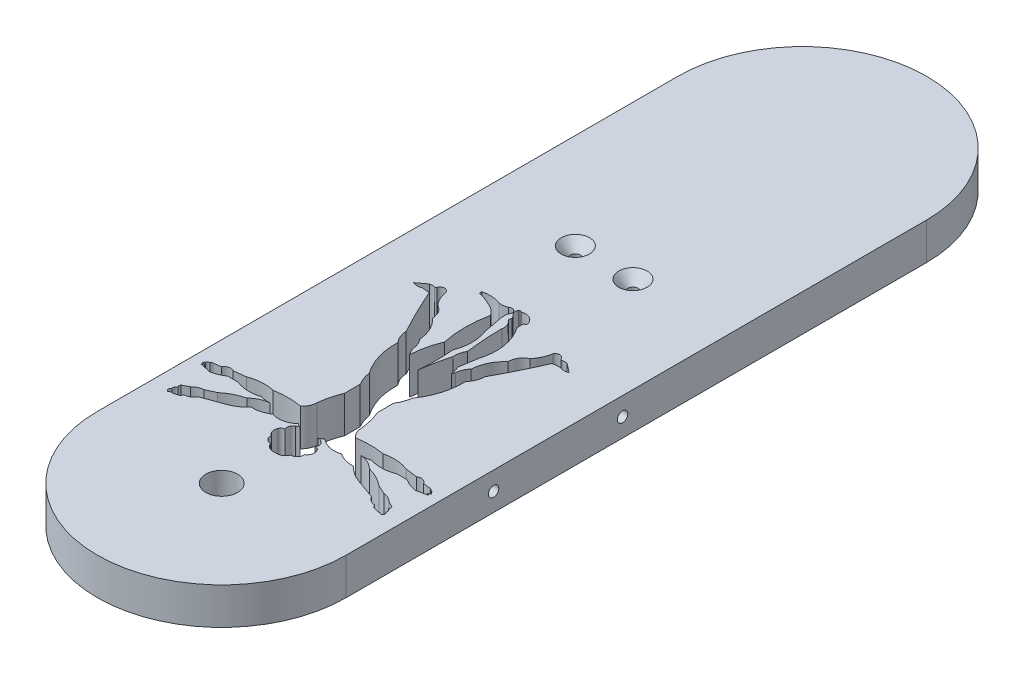
SolidWorks part; units mm, degrees
ref_plane "Front Plane" through (0, 0, 0) normal (0, 0, 1) x (1, 0, 0)
ref_plane "Top Plane" through (0, 0, 0) normal (0, 1, 0) x (1, 0, 0)
ref_plane "Right Plane" through (0, 0, 0) normal (1, 0, 0) x (0, 0, -1)
sketch "Sketch1" plane through (0, 0, 0) normal (0, 1, 0) x (1, 0, 0)
  line L0 (34.29, 228.6) -> (34.29, 0) construction
  line L1 (0, 0) -> (68.58, 0)
  line L2 (0, 0) -> (0, 194.31)
  line L4 (68.58, 0) -> (68.58, 194.31)
  arc A0 (0, 194.31) -> (68.58, 194.31) centre (34.29, 194.31) cw
  circle A1 centre (42.2275, 139.7) radius 1.3589
  circle A2 centre (26.3525, 139.7) radius 1.3589
  circle A3 centre (34.29, 34.29) radius 4.3815
  dimension "D2" = 2.7178
  dimension "D6" = 8.763
  dimension "D1" = 139.7
  dimension "D3" = 7.9375
  dimension "D4" = 68.58
  dimension "D5" = 228.6
  dimension "D7" = 34.29
extrude "Boss-Extrude1" add sketch "Sketch1" along normal blind 10.16 contours L0 A0 L2 L1 A3 A2 | A0 L0 A3 L1 L4 A1 region at (51.1861, 0, -111.0362) region at (17.3939, 0, -111.0362)
sketch "Sketch2" plane through (0, 10.16, 0) normal (0, 1, 0) x (1, 0, 0)
  line L0 (37.6657, 49.1626) -> (12.67, 49.1626) construction
sketch "Sketch3" plane through (0, 10.16, 0) normal (0, 1, 0) x (1, 0, 0)
  line L0 (34.29, 44.1322) -> (34.29, 49.022) construction
  line L1 (16.0215, 53.7464) -> (10.4335, 51.7461)
  line L2 (8.1475, 50.2221) -> (7.4635, 49.4709)
  line L3 (7.4635, 49.4709) -> (5.8739, 49.0246)
  line L4 (5.5691, 49.1516) -> (4.8952, 48.796)
  line L5 (5.2762, 52.1488) -> (6.9835, 53.0497)
  line L6 (9.5235, 54.2181) -> (12.0615, 55.3865)
  line L7 (12.3155, 60.7046) -> (9.5215, 60.7046)
  line L8 (7.5911, 59.6886) -> (6.0671, 59.2608)
  line L9 (6.0671, 59.2608) -> (3.0191, 59.8958)
  line L10 (3.5164, 60.3002) -> (2.8814, 60.4526)
  line L11 (4.4181, 61.8242) -> (6.4501, 62.0782)
  line L12 (8.9901, 62.7132) -> (12.2921, 63.1259)
  line L13 (29.7165, 72.7271) -> (29.7165, 77.0451)
  line L14 (17.3467, 108.4395) -> (15.3147, 108.5919)
  line L15 (12.7747, 108.5919) -> (15.3147, 110.4969)
  line L16 (24.3978, 115.2304) -> (24.3978, 115.8654)
  line L17 (34.9642, 113.5979) -> (34.4562, 114.4778)
  line L18 (37.8399, 113.9698) -> (37.8399, 112.1252)
  line L19 (39.8719, 99.4252) -> (39.1099, 94.6597)
  line L20 (34.3038, 106.8669) -> (33.2878, 112.3279)
  line L21 (55.8053, 108.5919) -> (53.2653, 110.4969)
  line L22 (51.2333, 108.4395) -> (53.2653, 108.5919)
  line L23 (38.8635, 72.7271) -> (38.8635, 77.0451)
  line L24 (59.5899, 62.7132) -> (56.2879, 63.1259)
  line L25 (64.1619, 61.8242) -> (62.1299, 62.0782)
  line L26 (65.0636, 60.3002) -> (65.6986, 60.4526)
  line L27 (62.5129, 59.2608) -> (65.5609, 59.8958)
  line L28 (60.9889, 59.6886) -> (62.5129, 59.2608)
  line L29 (56.2645, 60.7046) -> (59.0585, 60.7046)
  line L30 (59.0565, 54.2181) -> (56.5185, 55.3865)
  line L31 (63.3038, 52.1488) -> (61.5965, 53.0497)
  line L32 (63.0109, 49.1516) -> (63.6848, 48.796)
  line L33 (61.1165, 49.4709) -> (62.7061, 49.0246)
  line L34 (60.4325, 50.2221) -> (61.1165, 49.4709)
  line L35 (52.5585, 53.7464) -> (58.1465, 51.7461)
  line L36 (0, 0) -> (68.58, 0) construction
  line L37 (34.29, 0) -> (34.29, 228.6) construction
  arc A0 (30.6265, 59.1058) -> (24.7845, 57.8358) centre (26.6393, 63.3756) cw
  arc A1 (24.7845, 57.8358) -> (20.2125, 56.5404) centre (20.5978, 63.8963) cw
  arc A2 (20.2125, 56.5404) -> (16.0215, 53.7464) centre (12.5118, 63.5512) cw
  arc A3 (10.4335, 51.7461) -> (8.1475, 50.2221) centre (7.9734, 52.9598) cw
  arc A4 (5.8739, 49.0246) -> (5.5691, 49.1516) centre (5.8536, 49.4051) cw
  arc A5 (4.8952, 48.796) -> (4.7682, 50.066) centre (5.1441, 49.4623) cw
  arc A6 (4.7682, 50.066) -> (5.2762, 51.2344) centre (5.5909, 50.403) cw
  arc A7 (5.2762, 51.2344) -> (5.2762, 52.1488) centre (5.7528, 51.6916) cw
  arc A8 (6.9835, 53.0497) -> (9.5235, 54.2181) centre (9.7347, 50.4139) cw
  arc A9 (12.0615, 55.3865) -> (17.3955, 58.1043) centre (20.4503, 45.5156) cw
  arc A10 (29.4778, 90.8649) -> (31.2558, 98.7389) centre (52.3151, 89.8458) cw
  arc A11 (17.3955, 58.1043) -> (21.7135, 60.1363) centre (22.4072, 53.0582) cw
  arc A12 (21.7135, 60.1363) -> (19.1735, 60.4506) centre (21.1436, 65.9504) cw
  arc A13 (19.1735, 60.4506) -> (12.3155, 60.7046) centre (16.0984, 70.1341) cw
  arc A14 (9.5215, 60.7046) -> (7.5911, 59.6886) centre (4.4828, 67.9363) cw
  arc A15 (3.0191, 59.8958) -> (3.5164, 60.3002) centre (3.5164, 59.7922) cw
  arc A16 (2.8814, 60.4526) -> (3.1989, 60.9606) centre (3.3331, 60.5235) cw
  arc A17 (3.1989, 60.9606) -> (3.9101, 61.4686) centre (3.8223, 60.8397) cw
  arc A18 (3.9101, 61.4686) -> (4.4181, 61.8242) centre (4.3568, 61.3711) cw
  arc A19 (6.4501, 62.0782) -> (8.9901, 62.7132) centre (8.0119, 61.2284) cw
  arc A20 (12.2921, 63.1259) -> (19.1501, 63.5831) centre (16.4462, 52.4775) cw
  arc A21 (19.1501, 63.5831) -> (26.7701, 63.5831) centre (22.9601, 41.5582) cw
  arc A22 (26.7701, 63.5831) -> (28.1925, 66.6311) centre (23.8774, 66.7889) ccw
  arc A23 (28.1925, 66.6311) -> (29.7165, 72.7271) centre (49.926, 64.4363) cw
  arc A24 (29.7165, 77.0451) -> (28.2687, 81.0075) centre (39.544, 82.8816) cw
  arc A25 (28.2687, 81.0075) -> (24.9667, 92.1835) centre (43.2422, 91.5073) cw
  arc A26 (24.9667, 92.1835) -> (23.4427, 95.9935) centre (29.2833, 96.12) cw
  arc A27 (23.4427, 95.9935) -> (17.3467, 108.4395) centre (162.598, 171.8671) cw
  arc A28 (15.3147, 108.5919) -> (12.7747, 108.5919) centre (14.0447, 111.9134) cw
  arc A29 (15.3147, 110.4969) -> (16.7103, 110.4969) centre (16.0125, 108.0546) cw
  arc A30 (16.7103, 110.4969) -> (17.1861, 110.6747) centre (16.7942, 110.9979) ccw
  arc A31 (17.1861, 110.6747) -> (19.5718, 110.8293) centre (18.4067, 110.3239) cw
  arc A32 (19.5718, 110.8293) -> (21.6038, 106.5113) centre (28.3365, 112.3167) ccw
  arc A33 (21.6038, 106.5113) -> (23.8898, 102.8029) centre (19.8262, 102.8567) cw
  arc A34 (23.8898, 102.8029) -> (27.1918, 95.9449) centre (17.0531, 95.2872) cw
  arc A35 (27.1918, 95.9449) -> (28.4618, 92.8969) centre (23.3921, 92.5731) cw
  arc A36 (28.4618, 92.8969) -> (29.4778, 90.8649) centre (37.0851, 95.9385) ccw
  arc A37 (40.1182, 92.8969) -> (39.8033, 92.1197) centre (31.4949, 95.9385) cw
  arc A38 (41.3882, 95.9449) -> (40.1182, 92.8969) centre (45.1879, 92.5731) ccw
  arc A39 (31.2558, 98.7389) -> (31.2558, 111.4389) centre (61.067, 105.0889) cw
  arc A40 (31.2558, 111.4389) -> (28.9698, 113.4709) centre (25.8446, 107.6532) ccw
  arc A43 (24.3978, 115.8654) -> (29.4778, 115.5606) centre (26.4595, 107.7409) cw
  arc A44 (29.4778, 115.5606) -> (31.7638, 115.8146) centre (30.1904, 119.5617) ccw
  arc A45 (31.7638, 115.8146) -> (33.2878, 114.1795) centre (32.5258, 114.9971) cw
  arc A46 (33.2878, 114.1795) -> (33.2878, 112.3279) centre (39.056, 113.2537) ccw
  arc A47 (44.6902, 102.8029) -> (41.3882, 95.9449) centre (51.5269, 95.2872) ccw
  arc A48 (34.3038, 106.8669) -> (34.3038, 97.9769) centre (22.951, 102.4219) cw
  arc A49 (34.3038, 97.9769) -> (34.3038, 88.3249) centre (-18.0522, 93.1509) cw
  arc A50 (34.3038, 88.3249) -> (35.904, 96.4529) centre (90.5303, 81.4768) cw
  arc A51 (35.904, 96.4529) -> (36.666, 99.6279) centre (41.2228, 96.8553) cw
  arc A52 (36.666, 99.6279) -> (35.9802, 109.7879) centre (122.3372, 110.5138) cw
  arc A53 (35.9802, 109.7879) -> (34.9642, 112.5819) centre (33.2489, 110.3764) ccw
  arc A54 (34.9642, 112.5819) -> (34.9642, 113.5979) centre (35.5322, 113.0899) cw
  arc A55 (34.4562, 114.4778) -> (33.9482, 116.5098) centre (35.172, 115.7362) cw
  arc A56 (33.9482, 116.5098) -> (34.6594, 116.4336) centre (34.2654, 116.1129) cw
  arc A57 (34.6594, 116.4336) -> (38.3678, 114.6556) centre (35.6958, 113.8389) cw
  arc A58 (38.3678, 114.6556) -> (37.8399, 113.9698) centre (37.893, 114.475) cw
  arc A59 (37.8399, 112.1252) -> (39.8719, 99.4252) centre (26.0474, 103.7258) cw
  arc A60 (39.1099, 94.6597) -> (39.8033, 92.1197) centre (25.0555, 89.4582) cw
  arc A61 (30.6265, 59.1058) -> (31.817, 58.3438) centre (33.9337, 62.9618) ccw
  arc A62 (34.29, 49.022) -> (31.496, 50.546) centre (33.7777, 51.406) cw
  arc A63 (31.496, 50.546) -> (29.718, 52.578) centre (31.4778, 52.3239) cw
  arc A64 (29.718, 52.578) -> (28.956, 55.118) centre (30.6471, 54.241) cw
  arc A65 (28.956, 55.118) -> (30.1152, 55.88) centre (29.9434, 54.8786) cw
  arc A66 (30.1152, 55.88) -> (30.801, 58.0898) centre (31.4278, 56.684) cw
  arc A67 (30.801, 58.0898) -> (31.817, 58.3438) centre (31.4677, 57.5818) cw
  arc A68 (46.9762, 106.5113) -> (44.6902, 102.8029) centre (48.7538, 102.8567) ccw
  arc A69 (49.0082, 110.8293) -> (46.9762, 106.5113) centre (40.2435, 112.3167) cw
  arc A70 (51.3939, 110.6747) -> (49.0082, 110.8293) centre (50.1733, 110.3239) ccw
  arc A71 (51.8697, 110.4969) -> (51.3939, 110.6747) centre (51.7858, 110.9979) cw
  arc A72 (53.2653, 110.4969) -> (51.8697, 110.4969) centre (52.5675, 108.0546) ccw
  arc A73 (53.2653, 108.5919) -> (55.8053, 108.5919) centre (54.5353, 111.9134) ccw
  arc A74 (45.1373, 95.9935) -> (51.2333, 108.4395) centre (-94.018, 171.8671) ccw
  arc A75 (43.6133, 92.1835) -> (45.1373, 95.9935) centre (39.2967, 96.12) ccw
  arc A76 (40.3113, 81.0075) -> (43.6133, 92.1835) centre (25.3378, 91.5073) ccw
  arc A77 (38.8635, 77.0451) -> (40.3113, 81.0075) centre (29.036, 82.8816) ccw
  arc A78 (37.779, 58.0898) -> (36.763, 58.3438) centre (37.1123, 57.5818) ccw
  arc A79 (38.4648, 55.88) -> (37.779, 58.0898) centre (37.1522, 56.684) ccw
  arc A80 (39.624, 55.118) -> (38.4648, 55.88) centre (38.6366, 54.8786) ccw
  arc A81 (38.862, 52.578) -> (39.624, 55.118) centre (37.9329, 54.241) ccw
  arc A82 (37.084, 50.546) -> (38.862, 52.578) centre (37.1022, 52.3239) ccw
  arc A83 (34.29, 49.022) -> (37.084, 50.546) centre (34.8023, 51.406) ccw
  arc A84 (37.9535, 59.1058) -> (36.763, 58.3438) centre (34.6463, 62.9618) cw
  arc A85 (40.3875, 66.6311) -> (38.8635, 72.7271) centre (18.654, 64.4363) ccw
  arc A86 (41.8099, 63.5831) -> (40.3875, 66.6311) centre (44.7026, 66.7889) cw
  arc A87 (49.4299, 63.5831) -> (41.8099, 63.5831) centre (45.6199, 41.5582) ccw
  arc A88 (56.2879, 63.1259) -> (49.4299, 63.5831) centre (52.1338, 52.4775) ccw
  arc A89 (62.1299, 62.0782) -> (59.5899, 62.7132) centre (60.5681, 61.2284) ccw
  arc A90 (64.6699, 61.4686) -> (64.1619, 61.8242) centre (64.2232, 61.3711) ccw
  arc A91 (65.3811, 60.9606) -> (64.6699, 61.4686) centre (64.7577, 60.8397) ccw
  arc A92 (65.6986, 60.4526) -> (65.3811, 60.9606) centre (65.2469, 60.5235) ccw
  arc A93 (65.5609, 59.8958) -> (65.0636, 60.3002) centre (65.0636, 59.7922) ccw
  arc A94 (59.0585, 60.7046) -> (60.9889, 59.6886) centre (64.0972, 67.9363) ccw
  arc A95 (49.4065, 60.4506) -> (56.2645, 60.7046) centre (52.4816, 70.1341) ccw
  arc A96 (46.8665, 60.1363) -> (49.4065, 60.4506) centre (47.4364, 65.9504) ccw
  arc A97 (51.1845, 58.1043) -> (46.8665, 60.1363) centre (46.1728, 53.0582) ccw
  arc A98 (56.5185, 55.3865) -> (51.1845, 58.1043) centre (48.1297, 45.5156) ccw
  arc A99 (61.5965, 53.0497) -> (59.0565, 54.2181) centre (58.8453, 50.4139) ccw
  arc A100 (63.3038, 51.2344) -> (63.3038, 52.1488) centre (62.8272, 51.6916) ccw
  arc A101 (63.8118, 50.066) -> (63.3038, 51.2344) centre (62.9891, 50.403) ccw
  arc A102 (63.6848, 48.796) -> (63.8118, 50.066) centre (63.4359, 49.4623) ccw
  arc A103 (62.7061, 49.0246) -> (63.0109, 49.1516) centre (62.7264, 49.4051) ccw
  arc A104 (58.1465, 51.7461) -> (60.4325, 50.2221) centre (60.6066, 52.9598) ccw
  arc A105 (48.3675, 56.5404) -> (52.5585, 53.7464) centre (56.0682, 63.5512) ccw
  arc A106 (43.7955, 57.8358) -> (48.3675, 56.5404) centre (47.9822, 63.8963) ccw
  arc A107 (37.9535, 59.1058) -> (43.7955, 57.8358) centre (41.9407, 63.3756) ccw
  arc A108 (28.9698, 113.4709) -> (24.3978, 115.2304) centre (19.7144, 96.2415) ccw
  arc A110 (68.58, 194.31) -> (0, 194.31) centre (34.29, 194.31) ccw construction
  circle A111 centre (34.29, 34.29) radius 4.3815 construction
  point P178 (18.3246, 111.5913)
  dimension "D1" = 2.4384
  dimension "D2" = 1.778
  dimension "D3" = 1.905
  dimension "D4" = 1.016
  dimension "D5" = 1.5392
  dimension "D6" = 0.8382
  dimension "D7" = 5.08
  dimension "D8" = 5.842
  dimension "D9" = 7.366
  dimension "D10" = 10.414
  dimension "D31" = 2.7432
  dimension "D37" = 0.381
  dimension "D43" = 0.7112
  dimension "D44" = 0.889
  dimension "D45" = 0.6604
  dimension "D47" = 3.81
  dimension "D49" = 12.954
  dimension "D50" = 7.112
  dimension "D51" = 4.318
  dimension "D52" = 5.842
  dimension "D53" = 10.16
  dimension "D68" = 8.8139
  dimension "D74" = 0.508
  dimension "D78" = 0.4572
  dimension "D82" = 0.635
  dimension "D85" = 0.4572
  dimension "D90" = 1.778
  dimension "D94" = 11.43
  dimension "D98" = 22.352
  dimension "D99" = 4.318
  dimension "D102" = 21.844
  dimension "D106" = 11.43
  dimension "D111" = 18.288
  dimension "D112" = 5.842
  dimension "D115" = 158.496
  dimension "D119" = 3.556
  dimension "D123" = 2.54
  dimension "D126" = 0.508
  dimension "D127" = 1.27
  dimension "D132" = 8.89
  dimension "D135" = 4.064
  dimension "D138" = 10.16
  dimension "D141" = 5.08
  dimension "D143" = 9.144
  dimension "D147" = 22.86
  dimension "D148" = 30.48
  dimension "D149" = 7.874
  dimension "D151" = 6.604
  dimension "D154" = 52.578
  dimension "D156" = 12.192
  dimension "D157" = 56.642
  dimension "D166" = 19.558
  dimension "D168" = 8.382
  dimension "D172" = 4.064
  dimension "D173" = 1.1176
  dimension "D177" = 5.842
  dimension "D178" = 14.986
  dimension "D184" = 5.334
  dimension "D187" = 86.36
  dimension "D188" = 14.478
  dimension "D193" = 2.794
  dimension "D196" = 0.762
  dimension "D200" = 1.4478
  dimension "D203" = 0.508
  dimension "D204" = 2.794
  dimension "D205" = 0.508
  dimension "D211" = 14.732
  dimension "D12" = 1.524
  dimension "D13" = 2.032
  dimension "D14" = 2.794
  dimension "D15" = 1.778
  dimension "D16" = 2.54
  dimension "D17" = 0.762
  dimension "D18" = 0.762
  dimension "D19" = 1.1592
  dimension "D20" = 2.2098
  dimension "D21" = 0.6858
  dimension "D22" = 0.254
  dimension "D23" = 1.016
  dimension "D24" = 5.842
  dimension "D25" = 1.27
  dimension "D26" = 4.572
  dimension "D27" = 1.2954
  dimension "D28" = 0.762
  dimension "D29" = 4.191
  dimension "D30" = 2.794
  dimension "D32" = 1.016
  dimension "D33" = 1.651
  dimension "D34" = 1.524
  dimension "D35" = 2.286
  dimension "D36" = 5.588
  dimension "D38" = 0.3048
  dimension "D39" = 0.127
  dimension "D40" = 0.762
  dimension "D41" = 0.3556
  dimension "D42" = 148
  dimension "D46" = 1.9304
  dimension "D48" = 2.794
  dimension "D54" = 0.127
  dimension "D55" = 1.27
  dimension "D56" = 0.508
  dimension "D57" = 1.1684
  dimension "D58" = 0.9144
  dimension "D59" = 1.1684
  dimension "D60" = 2.54
  dimension "D61" = 1.1684
  dimension "D62" = 2.7178
  dimension "D63" = 5.334
  dimension "D64" = 2.032
  dimension "D65" = 6.858
  dimension "D66" = 0.254
  dimension "D67" = 2.54
  dimension "D69" = 1.524
  dimension "D70" = 1.9304
  dimension "D71" = 1.016
  dimension "D72" = 2.794
  dimension "D73" = 3.048
  dimension "D75" = 0.635
  dimension "D76" = 0.635
  dimension "D77" = 0.508
  dimension "D79" = 0.4044
  dimension "D80" = 0.1524
  dimension "D81" = 0.3175
  dimension "D83" = 0.7112
  dimension "D84" = 0.508
  dimension "D86" = 0.3556
  dimension "D87" = 0.508
  dimension "D88" = 2.032
  dimension "D89" = 0.254
  dimension "D91" = 0.635
  dimension "D92" = 2.54
  dimension "D93" = 3.302
  dimension "D95" = 6.858
  dimension "D96" = 0.4572
  dimension "D97" = 7.62
  dimension "D100" = 1.4224
  dimension "D101" = 3.048
  dimension "D103" = 6.096
  dimension "D104" = 1.524
  dimension "D105" = 4.318
  dimension "D107" = 3.9624
  dimension "D108" = 1.4478
  dimension "D109" = 3.302
  dimension "D110" = 11.176
  dimension "D113" = 3.81
  dimension "D114" = 1.524
  dimension "D116" = 6.096
  dimension "D117" = 12.446
  dimension "D118" = 2.032
  dimension "D120" = 0.1524
  dimension "D121" = 2.54
  dimension "D122" = 3.175
  dimension "D124" = 1.3956
  dimension "D125" = 2.54
  dimension "D128" = 0.4758
  dimension "D129" = 0.1778
  dimension "D130" = 0.1546
  dimension "D131" = 0.762
  dimension "D133" = 4.318
  dimension "D134" = 2.032
  dimension "D136" = 2.286
  dimension "D137" = 3.7084
  dimension "D139" = 6.858
  dimension "D140" = 3.302
  dimension "D142" = 1.27
  dimension "D144" = 3.048
  dimension "D145" = 2.032
  dimension "D146" = 1.016
  dimension "D150" = 1.778
  dimension "D152" = 12.7
  dimension "D153" = 9.652
  dimension "D155" = 8.89
  dimension "D158" = 1.6002
  dimension "D159" = 8.128
  dimension "D160" = 2.54
  dimension "D161" = 4.826
  dimension "D162" = 1.016
  dimension "D163" = 5.461
  dimension "D164" = 2.286
  dimension "D165" = 2.032
  dimension "D167" = 0.635
  dimension "D169" = 6.858
  dimension "D170" = 5.08
  dimension "D171" = 0.3048
  dimension "D174" = 2.286
  dimension "D175" = 0.254
  dimension "D176" = 2.2352
  dimension "D179" = 0.6934
  dimension "D180" = 2.54
  dimension "D181" = 3.81
  dimension "D182" = 4.826
  dimension "D183" = 0.762
  dimension "D185" = 0.762
  dimension "D186" = 3.175
  dimension "D189" = 2.032
  dimension "D190" = 0.6858
  dimension "D191" = 12.7
  dimension "D192" = 10.16
  dimension "D194" = 1.016
  dimension "D195" = 2.794
  dimension "D197" = 1.016
  dimension "D198" = 1.016
  dimension "D199" = 0.508
  dimension "D201" = 0.508
  dimension "D202" = 2.032
  dimension "D206" = 0.0762
  dimension "D207" = 0.7112
  dimension "D208" = 1.778
  dimension "D209" = 3.7084
  dimension "D210" = 0.6858
extrude "Cut-Extrude1" cut sketch "Sketch3" against normal through all
fillet "Fillet1" 2 edges at (0, 5.08, 0) (68.58, 5.08, 0) type full round first side face at (0, 5.08, -97.155) second side face at (68.58, 5.08, -97.155) middle face at (34.29, 5.08, 0)
hole_wizard "CSK for #3 Flat Head Machine Screw1" positions "Sketch6" profile "Sketch7" countersink size "#3" standard "ANSI Inch" end condition through all
sketch "Sketch6" plane through (0, 10.16, 0) normal (0, 1, 0) x (1, 0, 0)
  point P0 (42.2275, 139.7)
  point P3 (26.3525, 139.7)
sketch "Sketch7" plane through (42.2275, 10.16, -139.7) normal (1, 0, 0) x (0, 0, 1)
  line L0 (0, 0) -> (0, 10.16)
  line L1 (0, 10.16) -> (1.397, 10.16)
  line L2 (1.397, 10.16) -> (1.397, 2.8781)
  line L3 (1.397, 2.8781) -> (3.8989, 0)
  line L5 (3.8989, 0) -> (0, 0)
  line L6 (-1.397, 2.8781) -> (-3.8989, 0) construction
  line L11 (0, -6.35) -> (0, 107.95) construction
  dimension "Thru Hole Dia." = 2.794
  dimension "Thru Hole Depth" = 10.16
  dimension "Near C'Sink Dia." = 7.7978
  dimension "Near C'Sink Angle" = 82
sketch "Sketch8" plane through (0, 0, 0) normal (-1, 0, 0) x (0, 0, 1)
  line L0 (-34.29, 10.16) -> (-194.31, 10.16) construction
  line L2 (-34.29, 0) -> (-34.29, 10.16) construction
  circle A0 centre (-110.49, 5.08) radius 1.3589
  point P8 (-141.2155, 3.81)
  dimension "D2" = 2.7178
  dimension "D1" = 76.2
  dimension "D3" = 5.08
hole_wizard "#6-40 Tapped Hole1" positions "Sketch9" profile "Sketch11" tap size "#6-40" standard "ANSI Inch"
sketch "Sketch9" plane through (0, 0, 0) normal (-1, 0, 0) x (0, 0, 1)
  point P0 (-110.49, 5.08)
sketch "Sketch11" plane through (0, 5.08, -110.49) normal (0, 1, 0) x (0, 0, 1)
  line L0 (0, 0) -> (0, 9.7523)
  line L1 (0, 9.7523) -> (1.4351, 8.89)
  line L2 (1.4351, 8.89) -> (1.4351, 0)
  line L5 (1.4351, 0) -> (0, 0)
  line L10 (0, 9.7523) -> (-1.4351, 8.89) construction
  line L11 (0, -6.35) -> (0, 107.95) construction
  dimension "Tap Drill Dia." = 2.8702
  dimension "Tap Drill Depth" = 8.89
  dimension "Drill Angle" = 118
cosmetic thread "Hole Thread2" parameters "D1"=5.08, "D2"=3.5052
sketch "Sketch12" plane through (0, 10.16, 0) normal (0, 1, 0) x (1, 0, 0)
  line L0 (34.29, 0) -> (34.29, 228.6) construction
  arc A0 (0, 34.29) -> (68.58, 34.29) centre (34.29, 34.29) ccw construction
  arc A1 (68.58, 194.31) -> (0, 194.31) centre (34.29, 194.31) ccw construction
ref_plane "Plane1" through (34.29, 0, 0) normal (1, 0, 0) x (0, 0, -1)
sketch "Sketch13" plane through (0, 0, 0) normal (-1, 0, 0) x (0, 0, 1)
  line L0 (-92.71, 10.16) -> (-92.71, 0) construction
  line L1 (0, 10.16) -> (-228.6, 10.16) construction
  line L2 (-34.29, 0) -> (-194.31, 0) construction
  circle A0 centre (-110.49, 5.08) radius 1.3589 construction
  dimension "D1" = 17.78
ref_plane "Plane2" through (0, 0, -92.71) normal (0, 0, -1) x (0, -1, 0)
mirror "Mirror2" about plane through (0, 0, -92.71) normal (0, 0, -1) of "#6-40 Tapped Hole1"
mirror "Mirror3" about plane through (34.29, 0, 0) normal (1, 0, 0) of "Mirror2", "#6-40 Tapped Hole1"
